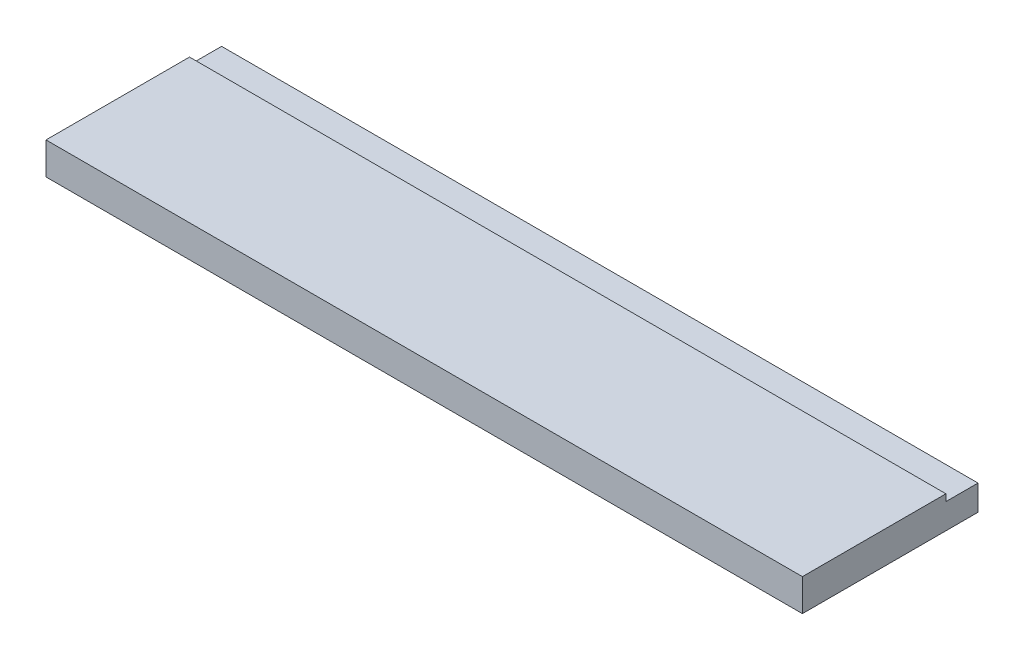
SolidWorks part; units mm, degrees
ref_plane "前视基准面" through (0, 0, 0) normal (0, 0, 1) x (1, 0, 0)
ref_plane "上视基准面" through (0, 0, 0) normal (0, 1, 0) x (1, 0, 0)
ref_plane "右视基准面" through (0, 0, 0) normal (1, 0, 0) x (0, 0, -1)
sketch "草图1" plane through (0, 0, 0) normal (0, 1, 0) x (1, 0, 0)
  line L1 (0, 52) -> (224, 52)
  line L2 (0, 52) -> (0, 0)
  line L3 (0, 0) -> (224, 0)
  line L4 (224, 52) -> (224, 0)
  dimension "D1" = 224
  dimension "D2" = 52
extrude "凸台-拉伸1" add sketch "草图1" along normal blind 9.5
sketch "草图2" plane through (0, 9.5, 0) normal (0, 1, 0) x (1, 0, 0)
  line L0 (224, 0) -> (224, 52) construction
  line L1 (0, 52) -> (224, 52)
  line L2 (0, 52) -> (0, 42.5)
  line L3 (0, 42.5) -> (224, 42.5)
  line L4 (224, 52) -> (224, 42.5)
  dimension "D1" = 9.5
extrude "切除-拉伸1" cut sketch "草图2" against normal blind 2
